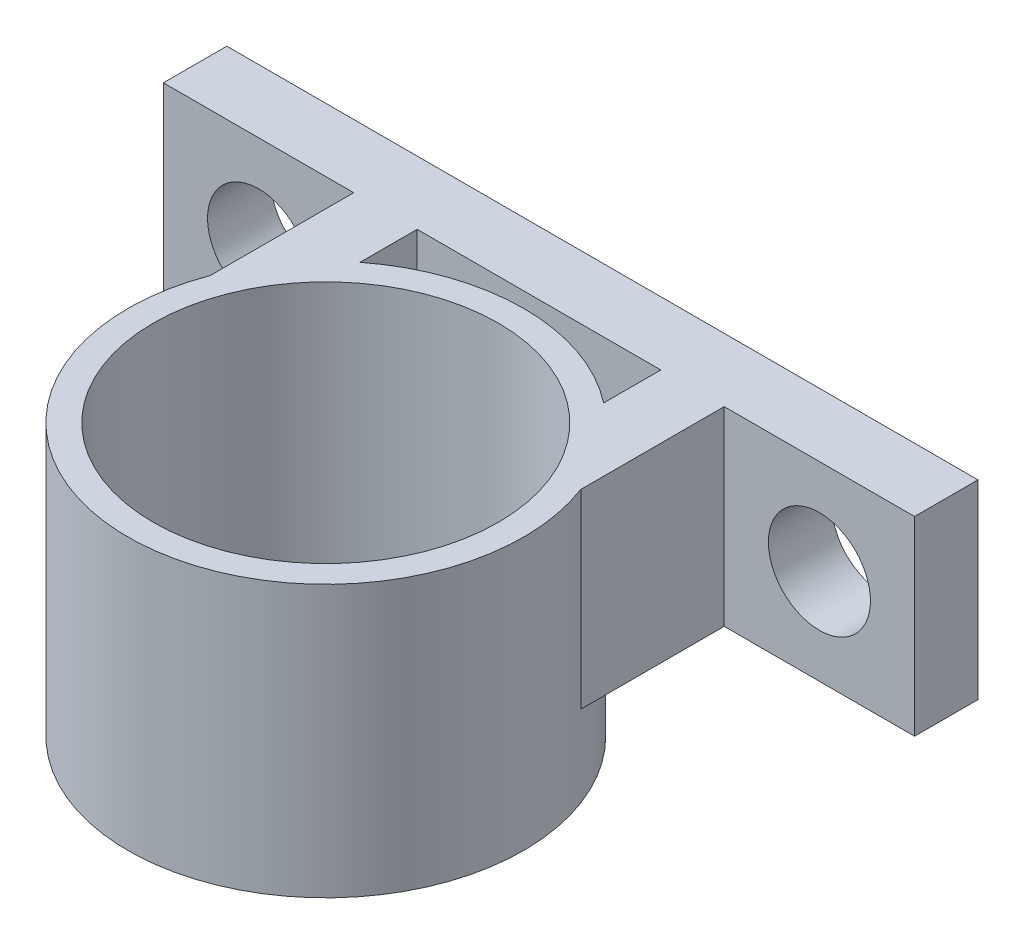
SolidWorks part; units mm, degrees
ref_plane "Front Plane" through (0, 0, 0) normal (0, 0, 1) x (1, 0, 0)
ref_plane "Top Plane" through (0, 0, 0) normal (0, 1, 0) x (1, 0, 0)
ref_plane "Right Plane" through (0, 0, 0) normal (1, 0, 0) x (0, 0, -1)
sketch "Sketch1" plane through (0, 0, 0) normal (0, 1, 0) x (1, 0, 0)
  line L0 (0, 0) -> (14.2506, 0) construction
  line L1 (0, 0) -> (0, 17.6258) construction
  line L3 (-6.096, -0.381) -> (-6.096, 13.843) construction
  line L4 (-9.271, 0) -> (-9.271, 10.668)
  line L5 (-9.271, 10.668) -> (-18.796, 10.668)
  line L6 (-6.096, 13.843) -> (-18.796, 13.843)
  line L7 (-18.796, 10.668) -> (-18.796, 13.843)
  line L9 (-6.096, 13.843) -> (6.096, 13.843)
  line L11 (9.271, 0) -> (9.271, 10.668)
  line L12 (18.796, 10.668) -> (18.796, 13.843)
  line L13 (6.096, 13.843) -> (18.796, 13.843)
  line L14 (9.271, 10.668) -> (18.796, 10.668)
  line L17 (-6.096, 6.731) -> (-6.096, 10.668)
  line L18 (6.096, 6.731) -> (6.096, 10.668)
  line L19 (-6.096, 10.668) -> (6.096, 10.668)
  circle A0 centre (0, 0) radius 6.096
  circle A1 centre (0, 0) radius 9.271 construction
  arc A3 (9.271, 0) -> (-9.271, 0) centre (0, 0) cw
  arc A5 (-6.096, 6.731) -> (6.096, 6.731) centre (0, 0) cw
  point P18 (0, 13.843)
  point P19 (0, 10.668)
  dimension "D1" = 12.192
  dimension "D2" = 3.175
  dimension "D3" = 14.224
  dimension "D4" = 3.175
  dimension "D5" = 12.7
extrude "Boss-Extrude1" add sketch "Sketch1" along normal blind 9.525
sketch "Sketch2" plane through (0, 0, -10.668) normal (0, 0, 1) x (1, 0, 0)
  line L0 (-18.796, 4.7625) -> (-9.271, 4.7625) construction
  line L1 (-18.796, 9.525) -> (-18.796, 0) construction
  line L2 (-9.271, 9.525) -> (-9.271, 0) construction
  line L3 (-14.0335, 9.525) -> (-14.0335, 0) construction
  line L4 (-18.796, 9.525) -> (-9.271, 9.525) construction
  line L5 (-18.796, 0) -> (-9.271, 0) construction
  line L6 (0, 0) -> (0, 9.525) construction
  line L7 (9.271, 9.525) -> (-9.271, 9.525) construction
  circle A0 centre (-14.0335, 4.7625) radius 2.5527
  circle A1 centre (14.0335, 4.7625) radius 2.5527
  dimension "D1" = 5.1054
extrude "Cut-Extrude1" cut sketch "Sketch2" against normal through all
sketch "Sketch3" plane through (0, 0, 0) normal (0, -1, 0) x (-1, 0, 0)
  circle A0 centre (0, 0) radius 6.096
  circle A3 centre (0, 0) radius 9.271
  arc A4 (-9.271, 0) -> (9.271, 0) centre (0, 0) ccw construction
  circle A5 centre (0, 0) radius 6.096 construction
  dimension "D1" = 0
  dimension "D2" = 0
extrude "Boss-Extrude2" add sketch "Sketch3" along normal blind 2.794
sketch "Sketch6" plane through (0, 9.525, 0) normal (0, 1, 0) x (1, 0, 0)
  circle A0 centre (0, 0) radius 8.636
  circle A1 centre (0, 0) radius 9.906
  dimension "D1" = 1.27
extrude "Boss-Extrude4" add sketch "Sketch6" against normal up to surface (12.319 mm away) up to face at (0, -2.794, -9.271)
sketch "Sketch5" plane through (0, 9.525, 0) normal (0, 1, 0) x (1, 0, 0)
  circle A0 centre (0, 0) radius 8.636
  dimension "D1" = 17.272
extrude "Cut-Extrude2" cut sketch "Sketch5" against normal up to surface (12.319 mm away) up to face at (0, -2.794, -6.096)
sketch "Sketch4" plane through (0, -2.794, 0) normal (0, -1, 0) x (-1, 0, 0)
  circle A2 centre (0, 0) radius 9.906
  circle A3 centre (0, 0) radius 7.366
  circle A4 centre (0, 0) radius 9.906 construction
  dimension "D1" = 0
  dimension "D2" = 14.732
extrude "Boss-Extrude3" add sketch "Sketch4" along normal blind 1.27 contours A2 | A3
